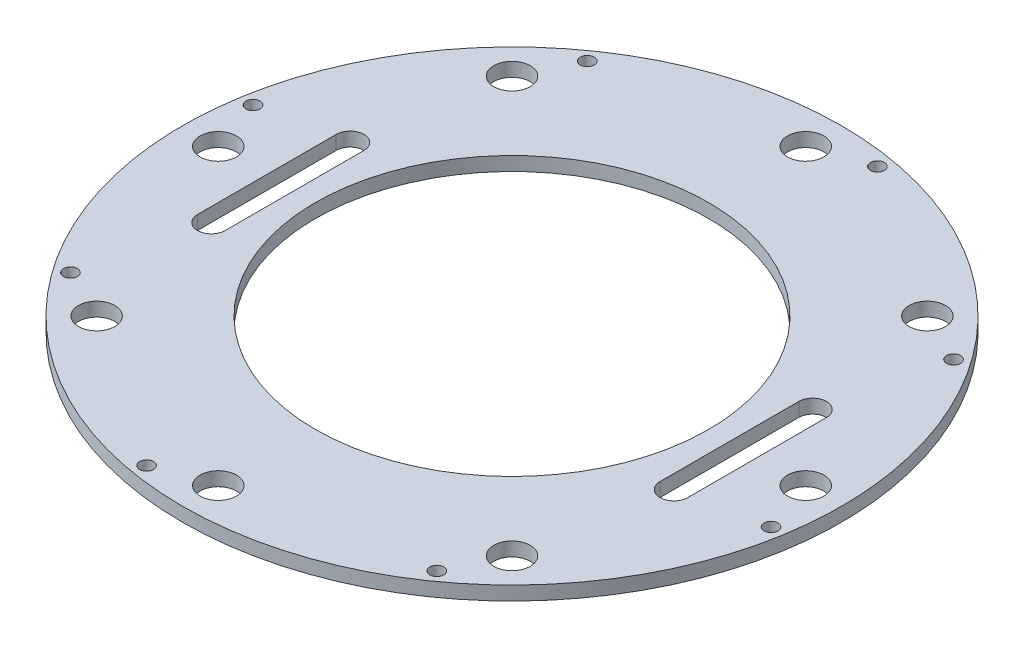
SolidWorks part; units mm, degrees
ref_plane "Front Plane" through (0, 0, 0) normal (0, 0, 1) x (1, 0, 0)
ref_plane "Top Plane" through (0, 0, 0) normal (0, 1, 0) x (1, 0, 0)
ref_plane "Right Plane" through (0, 0, 0) normal (1, 0, 0) x (0, 0, -1)
sketch "Sketch1" plane through (0, 0, 0) normal (0, 1, 0) x (1, 0, 0)
  line L0 (10, -3) -> (10, 3) construction
  line L1 (9.4, -3) -> (9.4, 3)
  line L2 (10.6, -3) -> (10.6, 3)
  line L3 (0, 0) -> (0, -14.25) construction
  line L4 (-10, -3) -> (-10, 3) construction
  line L5 (-9.4, -3) -> (-9.4, 3)
  line L6 (-10.6, -3) -> (-10.6, 3)
  line L7 (0, 0) -> (-13.1653, 5.4532) construction
  line L8 (0, 0) -> (-14.25, 0) construction
  circle A0 centre (0, 0) radius 14.25
  circle A1 centre (0, 0) radius 8.5
  arc A2 (9.4, -3) -> (10.6, -3) centre (10, -3) ccw
  arc A3 (10.6, 3) -> (9.4, 3) centre (10, 3) ccw
  arc A4 (-9.4, -3) -> (-10.6, -3) centre (-10, -3) cw
  arc A5 (-10.6, 3) -> (-9.4, 3) centre (-10, 3) cw
  circle A7 centre (-8.9803, -8.9803) radius 0.7874
  circle A8 centre (-12.7, 0) radius 0.7874
  circle A9 centre (-8.9803, 8.9803) radius 0.7874
  circle A10 centre (0, 12.7) radius 0.7874
  circle A11 centre (8.9803, 8.9803) radius 0.7874
  circle A12 centre (12.7, 0) radius 0.7874
  circle A13 centre (8.9803, -8.9803) radius 0.7874
  circle A14 centre (0, -12.7) radius 0.7874
  circle A15 centre (-13.5, 2.3) radius 0.3
  circle A17 centre (-7.9196, 11.1723) radius 0.3
  circle A18 centre (2.3, 13.5) radius 0.3
  circle A19 centre (11.1723, 7.9196) radius 0.3
  circle A20 centre (13.5, -2.3) radius 0.3
  circle A21 centre (7.9196, -11.1723) radius 0.3
  circle A22 centre (-2.3, -13.5) radius 0.3
  circle A23 centre (-11.1723, -7.9196) radius 0.3
  point P6 (10, 0)
  point P13 (-10, 0)
  point P38 (0, 0)
  point P44 (0, 0)
  point P58 (0, 0)
  point P61 (0, 0)
  dimension "D1" = 8
  dimension "D2" = 17
  dimension "D6" = 12.7
  dimension "D7" = 1.5748
  dimension "D12" = 0.6
  dimension "D3" = 1.2
  dimension "D4" = 6
  dimension "D5" = 10
  dimension "D8" = 12.7
  dimension "D9" = 8.9803
  dimension "D10" = 2.3
  dimension "D11" = 13.5
  dimension "D13" = 22.5
  dimension "D14" = 8
extrude "Boss-Extrude1" add sketch "Sketch1" along normal blind 0.6 contours A0 A3 L2 A2 L1 A1 L6 A5 L5 A4 region at (-13.8469, 0, 0)
